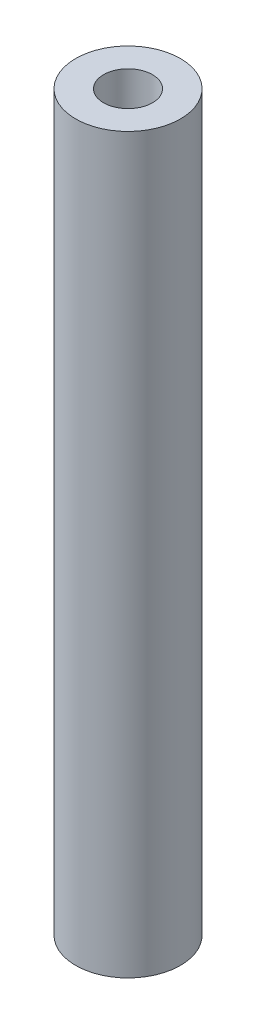
SolidWorks part; units mm, degrees
ref_plane "Front Plane" through (0, 0, 0) normal (0, 0, 1) x (1, 0, 0)
ref_plane "Top Plane" through (0, 0, 0) normal (0, 1, 0) x (1, 0, 0)
ref_plane "Right Plane" through (0, 0, 0) normal (1, 0, 0) x (0, 0, -1)
sketch "Sketch1" plane through (0, 0, 0) normal (0, 1, 0) x (1, 0, 0)
  circle A0 centre (0, 0) radius 3
  circle A1 centre (0, 0) radius 1.4
  dimension "D1" = 6
  dimension "D2" = 2.8
extrude "Boss-Extrude1" add sketch "Sketch1" along normal blind 42 contours A0 A1 region at (-2.9151, 0, 0)
extrude "Boss-Extrude2" add sketch "Sketch1<3>" along normal blind 22 from offset 10 contours A1
sketch "Sketch1<3>" plane through (0, 0, 0) normal (0, 1, 0) x (1, 0, 0) same geometry as "Sketch1"
